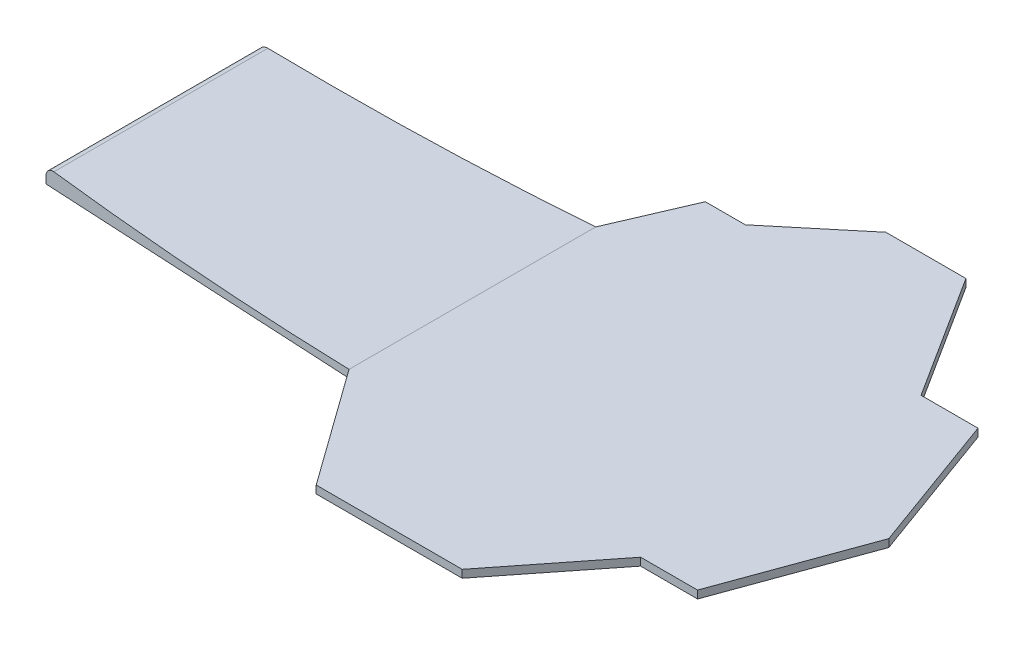
SolidWorks part; units mm, degrees
ref_plane "前视基准面" through (0, 0, 0) normal (0, 0, 1) x (1, 0, 0)
ref_plane "上视基准面" through (0, 0, 0) normal (0, 1, 0) x (1, 0, 0)
ref_plane "右视基准面" through (0, 0, 0) normal (1, 0, 0) x (0, 0, -1)
other "Configuration Table"
sketch "草图2" plane through (0, 0, 0) normal (0, 1, 0) x (1, 0, 0)
  line L0 (0, 0) -> (243.6421, 0) construction
  line L30 (176.8295, 36.1855) -> (82.5273, -31.8251) construction
  line L35 (141.8216, 68.0827) -> (121.1619, 68.0827)
  line L36 (176.8295, 36.1855) -> (190, 0)
  line L37 (104.1466, -61.9173) -> (82.5273, -31.8251)
  line L38 (82.5273, -31.8251) -> (0, -27.5)
  line L39 (0, -27.5) -> (0, 27.5)
  line L40 (0, 27.5) -> (82.5273, 31.8251)
  line L43 (190, 0) -> (176.8295, -36.1855)
  line L45 (82.5273, 31.8251) -> (91.0398, 51.6089)
  line L51 (104.1466, -61.9173) -> (190, 0) construction
  line L53 (141.8216, -61.9173) -> (104.1466, -61.9173)
  line L55 (82.5273, 31.8251) -> (342.4089, 31.8251) construction
  line L57 (176.8295, 36.1855) -> (176.8295, 0) construction
  line L58 (176.8295, 0) -> (176.8295, -36.1855) construction
  line L59 (82.5273, -31.8251) -> (342.4089, -31.8251) construction
  line L62 (91.0398, 51.6089) -> (101.351, 51.6089)
  line L63 (101.351, 51.6089) -> (121.1619, 68.0827)
  line L64 (141.8216, 68.0827) -> (162.1337, 36.1855)
  line L65 (162.1337, 36.1855) -> (176.8295, 36.1855)
  line L66 (176.8295, -36.1855) -> (162.1337, -36.1855)
  line L67 (162.1337, -36.1855) -> (141.8216, -61.9173)
  dimension "D1" = 190
  dimension "D2" = 130
  dimension "D4" = 55
  dimension "D6" = 93
  dimension "D7" = 93
  dimension "D8" = 140
extrude "凸台-拉伸1" add sketch "草图2" along normal blind 2
sketch "草图6" plane through (0, 2, 0) normal (0, 1, 0) x (1, 0, 0)
  line L0 (82.5273, 31.8251) -> (82.5273, -31.8251)
  line L1 (82.5273, -31.8251) -> (0, -27.5)
  line L2 (0, -27.5) -> (0, 27.5)
  line L3 (0, 27.5) -> (82.5273, 31.8251)
extrude "凸台-拉伸2" add sketch "草图6" along normal blind 2
sketch "草图7" plane through (0, 0, 0) normal (0, 0, 1) x (1, 0, 0)
  line L2 (82.5273, 2) -> (82.5273, 30.7408)
  line L3 (82.5273, 30.7408) -> (0, 4)
  spline S0 degree 2 poles (82.5273, 2) (41.2153, 1.0012) (0, 4) knots 0 0 0 1 1 1
extrude "切除-拉伸3" cut sketch "草图7" against normal through all both and the other way through all
fillet "圆角1" radius 2 1 edges at (0, 4, 0)
ref_plane "基准面3" through (0, -12, 0) normal (0, -1, 0) x (-1, 0, 0)
sketch "草图10" plane through (0, 0, 0) normal (0, -1, 0) x (1, 0, 0)
  line L0 (0, 27.5) -> (82.5273, 31.8251)
  line L1 (82.5273, 31.8251) -> (171.8529, 31.8251)
  line L2 (171.8529, 31.8251) -> (171.8529, -31.8251)
  line L3 (171.8529, -31.8251) -> (82.5273, -31.8251)
  line L4 (82.5273, -31.8251) -> (0, -27.5)
  line L5 (0, -27.5) -> (0, 27.5)
sketch "草图12" plane through (0, 2, 0) normal (0, 1, 0) x (1, 0, 0)
  line L0 (176.8295, 36.1855) -> (82.5273, -31.8251)
  line L1 (190, 0) -> (104.1466, -61.9173)
  line L2 (183.4148, 18.0928) -> (93.337, -46.8712) construction
  line L3 (190, 0) -> (176.8295, 36.1855) construction
  line L4 (82.5273, -31.8251) -> (104.1466, -61.9173) construction
